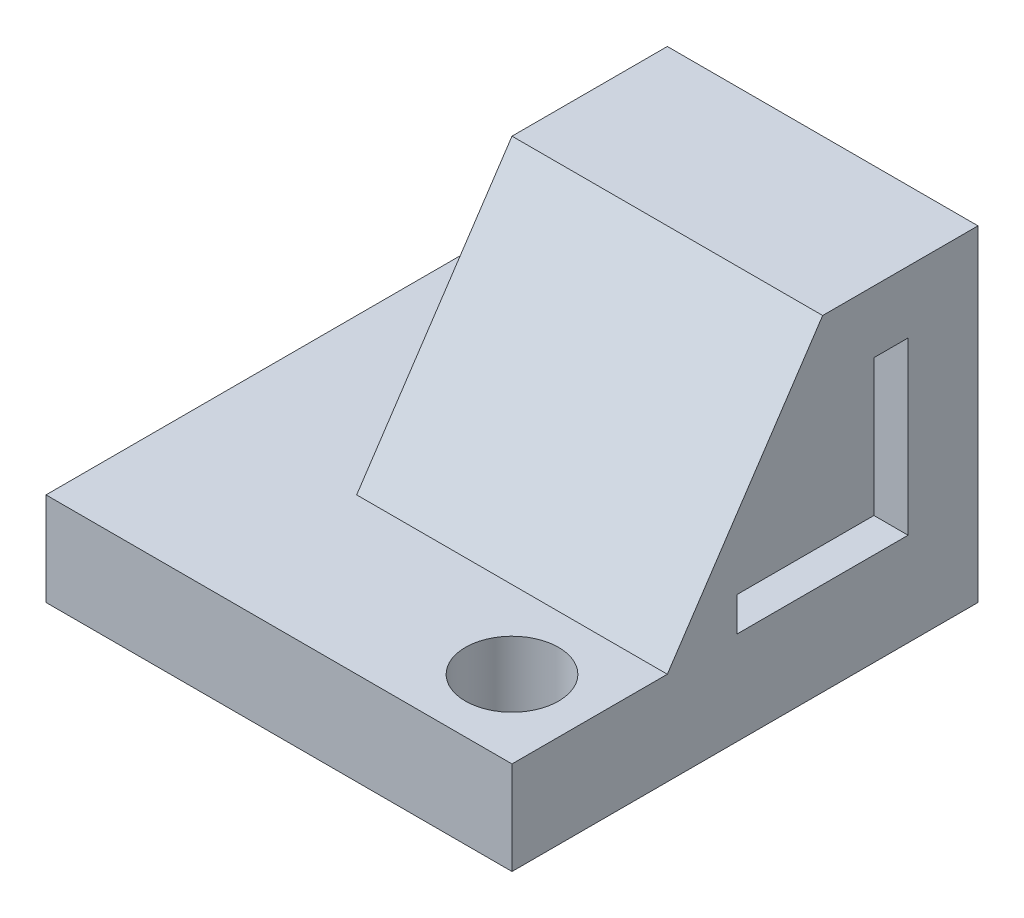
SolidWorks part; units mm, degrees
ref_plane "Front Plane" through (0, 0, 0) normal (0, 0, 1) x (1, 0, 0)
ref_plane "Top Plane" through (0, 0, 0) normal (0, 1, 0) x (1, 0, 0)
ref_plane "Right Plane" through (0, 0, 0) normal (1, 0, 0) x (0, 0, -1)
sketch "Sketch1" plane through (0, 0, 0) normal (0, 1, 0) x (1, 0, 0)
  line L1 (19.05, -19.05) -> (-19.05, -19.05)
  line L2 (19.05, -19.05) -> (19.05, 19.05)
  line L3 (19.05, 19.05) -> (-19.05, 19.05)
  line L4 (-19.05, -19.05) -> (-19.05, 19.05)
  line L5 (19.05, -19.05) -> (-19.05, 19.05) construction
  line L6 (19.05, 19.05) -> (-19.05, -19.05) construction
  point P0 (0, 0)
  dimension "D1" = 38.1
  dimension "D2" = 38.1
extrude "Boss-Extrude1" add sketch "Sketch1" along normal blind 7.62
sketch "Sketch2" plane through (0, 7.62, 0) normal (0, 1, 0) x (1, 0, 0)
  line L0 (19.05, 19.05) -> (-19.05, 19.05) construction
  line L1 (19.05, -6.35) -> (-6.35, -6.35)
  line L2 (19.05, -6.35) -> (19.05, 19.05)
  line L3 (19.05, 19.05) -> (-6.35, 19.05)
  line L4 (-6.35, -6.35) -> (-6.35, 19.05)
  line L5 (19.05, -6.35) -> (-6.35, 19.05) construction
  line L6 (19.05, 19.05) -> (-6.35, -6.35) construction
  line L7 (19.05, -19.05) -> (19.05, 19.05) construction
  point P0 (6.35, 6.35)
  point P9 (0, 0)
  point P11 (0, 0)
  dimension "D1" = 25.4
  dimension "D2" = 25.4
extrude "Boss-Extrude2" add sketch "Sketch2" along normal blind 19.05
sketch "Sketch3" plane through (0, 7.62, 0) normal (0, 1, 0) x (1, 0, 0)
  line L0 (-12.7, 12.7) -> (12.7, 12.7) construction
  line L1 (12.7, 12.7) -> (12.7, -12.7) construction
  line L2 (-12.7, 12.7) -> (-19.05, 12.7) construction
  line L3 (-19.05, 19.05) -> (-19.05, -19.05) construction
  line L4 (12.7, -12.7) -> (19.05, -12.7) construction
  line L5 (19.05, -19.05) -> (19.05, -6.35) construction
  line L6 (-12.7, 12.7) -> (-12.7, 19.05) construction
  line L9 (12.7, -12.7) -> (12.7, -19.05) construction
  line L10 (-19.05, -19.05) -> (19.05, -19.05) construction
  line L11 (-6.35, 19.05) -> (-19.05, 19.05) construction
  circle A0 centre (-12.7, 12.7) radius 3.81
  circle A1 centre (12.7, -12.7) radius 3.81
  point P4 (12.7, 14.1495)
  point P16 (0, 0)
  dimension "D3" = 7.62
  dimension "D1" = 25.4
  dimension "D2" = 25.4
extrude "Cut-Extrude1" cut sketch "Sketch3" against normal up to next
sketch "Sketch4" plane through (19.05, 0, 0) normal (1, 0, 0) x (0, 0, -1)
  line L0 (10.541, 21.59) -> (13.335, 21.59)
  line L1 (13.335, 21.59) -> (13.335, 7.62)
  line L2 (13.335, 7.62) -> (-0.635, 7.62)
  line L3 (-0.635, 7.62) -> (-0.635, 10.414)
  line L4 (-0.635, 10.414) -> (10.541, 10.414)
  line L5 (10.541, 10.414) -> (10.541, 21.59)
  line L6 (-6.35, 7.62) -> (19.05, 7.62) construction
  point P7 (6.35, 7.62)
  point P11 (6.35, 7.62)
  dimension "D1" = 2.794
  dimension "D2" = 13.97
extrude "Cut-Extrude2" cut sketch "Sketch4" against normal blind 6.35
sketch "Sketch5" plane through (19.05, 0, 0) normal (1, 0, 0) x (0, 0, -1)
  line L0 (6.35, 26.67) -> (-6.35, 7.62)
  line L1 (-6.35, 26.67) -> (19.05, 26.67) construction
  line L2 (-6.35, 7.62) -> (-6.35, 26.67)
  line L3 (-6.35, 26.67) -> (6.35, 26.67)
extrude "Cut-Extrude3" cut sketch "Sketch5" against normal up to next
